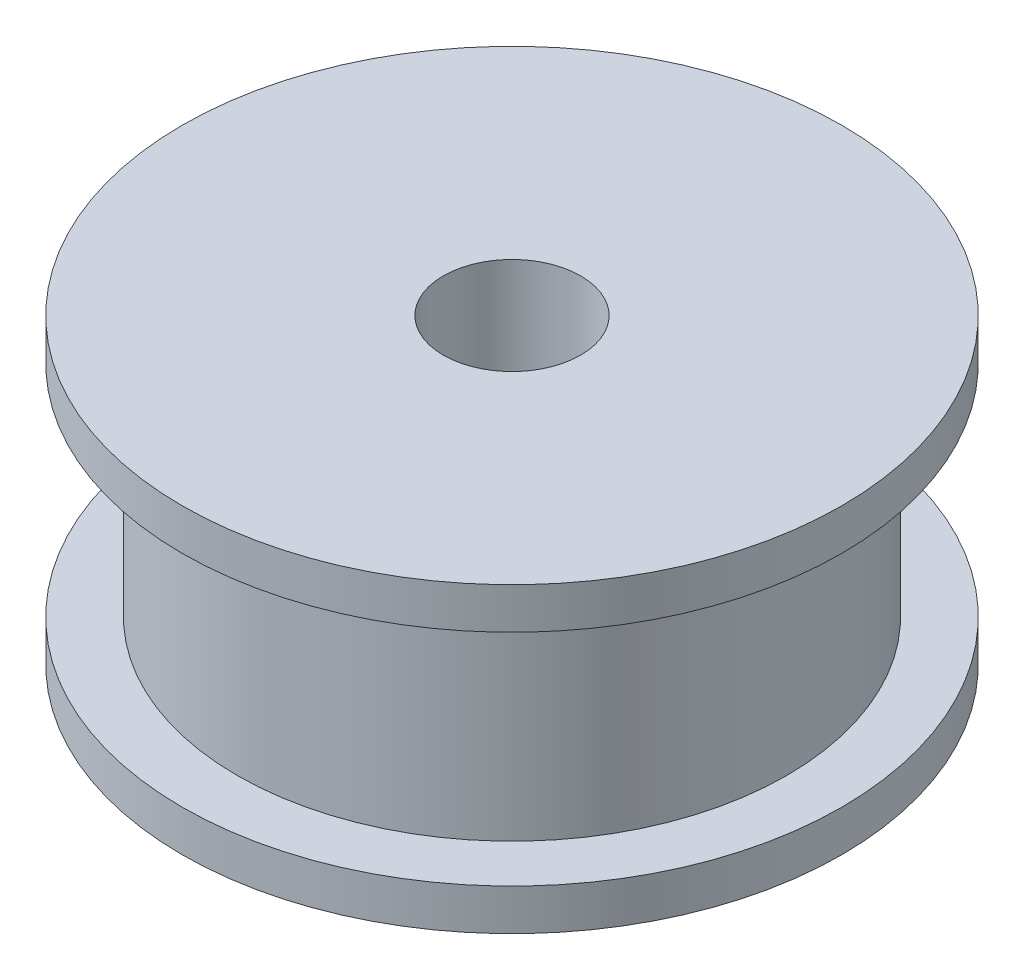
SolidWorks part; units mm, degrees
ref_plane "前视基准面" through (0, 0, 0) normal (0, 0, 1) x (1, 0, 0)
ref_plane "上视基准面" through (0, 0, 0) normal (0, 1, 0) x (1, 0, 0)
ref_plane "右视基准面" through (0, 0, 0) normal (1, 0, 0) x (0, 0, -1)
other "Configuration Table"
sketch "草图1" plane through (0, 0, 0) normal (0, 1, 0) x (1, 0, 0)
  circle A0 centre (0, 0) radius 20
  circle A1 centre (0, 0) radius 5
  dimension "D1" = 40
  dimension "D2" = 10
extrude "凸台-拉伸1" add sketch "草图1" along normal blind 16
sketch "草图2" plane through (0, 0, 0) normal (0, -1, 0) x (1, 0, 0)
  circle A2 centre (0, 0) radius 5 construction
  circle A3 centre (0, 0) radius 5
  circle A4 centre (0, 0) radius 24
  dimension "D1" = 48
extrude "凸台-拉伸2" add sketch "草图2" along normal blind 3
extrude "凸台-拉伸3" add sketch "草图2<2>" against normal blind 3 from surface starting at face at (0, 16, 20)
sketch "草图2<2>" plane through (0, 0, 0) normal (0, -1, 0) x (1, 0, 0) same geometry as "草图2"
